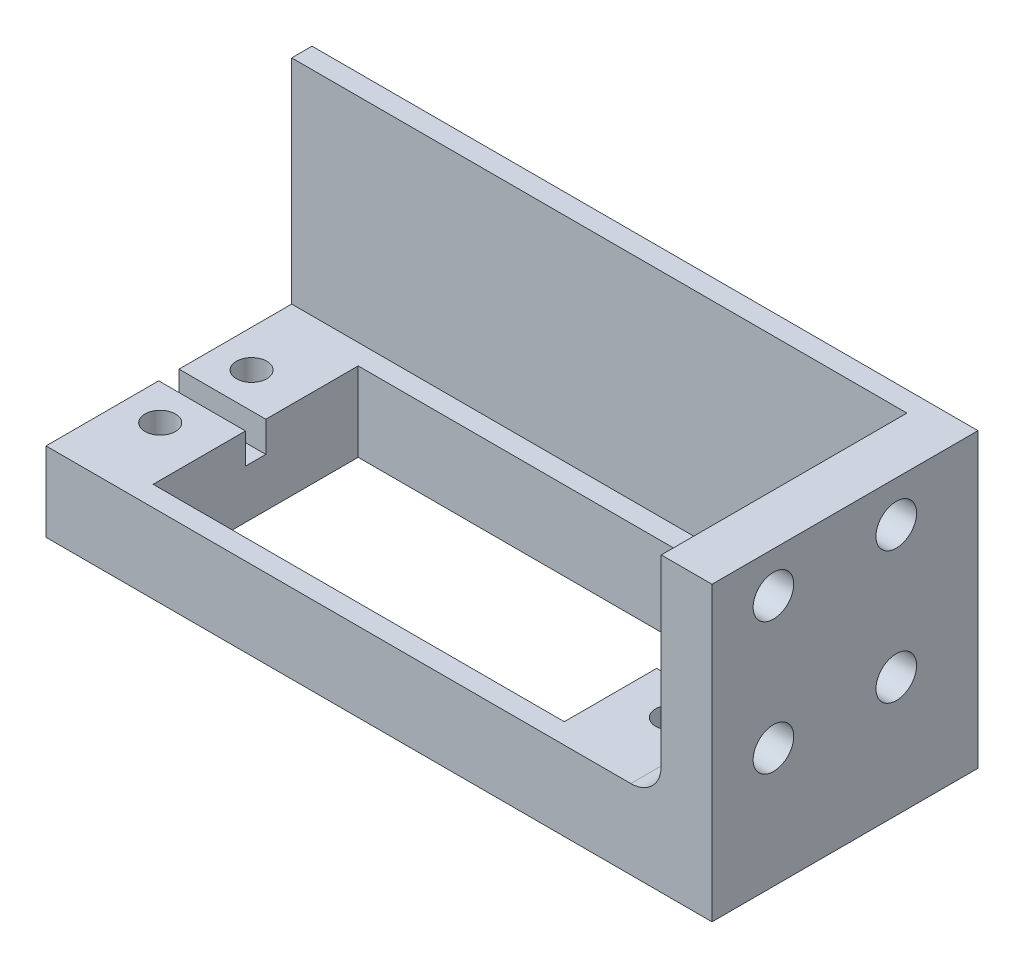
SolidWorks part; units mm, degrees
ref_plane "Front Plane" through (0, 0, 0) normal (0, 0, 1) x (1, 0, 0)
ref_plane "Top Plane" through (0, 0, 0) normal (0, 1, 0) x (1, 0, 0)
ref_plane "Right Plane" through (0, 0, 0) normal (1, 0, 0) x (0, 0, -1)
sketch "Sketch1" plane through (0, 0, 0) normal (0, 1, 0) x (1, 0, 0)
  line L0 (-101.8128, 12.4518) -> (-101.8128, 18.4813)
  line L1 (-101.8128, 21.4518) -> (-101.8128, 24.8665)
  line L2 (-94.5628, 5.4665) -> (-101.2128, 5.4665)
  line L3 (-95.1628, 6.0665) -> (-95.1628, 14.7945)
  line L4 (-54.8628, 14.7945) -> (-54.8628, 6.0665)
  line L5 (-48.2128, 18.4813) -> (-48.2128, 12.4518)
  line L6 (-85.1628, 25.4665) -> (-61.0205, 25.4665)
  line L7 (-95.2628, 25.4665) -> (-95.2628, 5.4665)
  line L8 (-101.8128, 25.4665) -> (-48.2128, 25.4665)
  line L9 (-101.8128, 25.4665) -> (-101.8128, 5.4665)
  line L10 (-101.8128, 5.4665) -> (-48.2128, 5.4665)
  line L11 (-48.2128, 25.4665) -> (-48.2128, 5.4665)
  line L12 (-95.1628, 25.4665) -> (-54.8628, 25.4665)
  line L13 (-95.1628, 25.4665) -> (-95.1628, 5.4665)
  line L14 (-95.1628, 5.4665) -> (-54.8628, 5.4665)
  line L15 (-54.8628, 25.4665) -> (-54.8628, 5.4665)
  line L17 (-54.7628, 25.4665) -> (-54.7628, 5.4665)
  line L19 (-95.2628, 25.5665) -> (-54.7628, 25.5665) construction
  line L20 (-95.2628, 5.3665) -> (-54.7628, 5.3665) construction
  line L22 (-95.2628, 25.5665) -> (-95.2628, 5.3665) construction
  line L23 (-54.7628, 25.5665) -> (-54.7628, 5.3665) construction
  circle A4 centre (-100.1628, 19.9665) radius 1.5
  circle A5 centre (-100.1628, 10.9665) radius 1.5
  circle A6 centre (-49.8628, 19.9665) radius 1.5
  circle A7 centre (-49.8628, 10.9665) radius 1.5
  dimension "D1" = 0.1
extrude "Boss-Extrude1" add sketch "Sketch1" along normal blind 7.8 contours L8 L17 L10 L11 L5 A7 A6 | L9 L10 L2 L7 L8 L1 L0 A5 A4
sketch "Sketch2" plane through (0, 7.8, 0) normal (0, 1, 0) x (1, 0, 0)
  line L5 (-101.8128, 25.4665) -> (-103.8128, 25.4665)
  line L6 (-101.8128, 25.4665) -> (-101.8128, 5.4665)
  line L7 (-101.8128, 5.4665) -> (-103.8128, 5.4665)
  line L8 (-101.8128, 25.4665) -> (-101.8128, 5.4665)
  line L9 (-101.8128, 5.4665) -> (-95.2628, 5.4665)
  line L10 (-95.2628, 5.4665) -> (-95.2628, 25.4665)
  line L11 (-95.2628, 25.4665) -> (-101.8128, 25.4665)
  line L12 (-101.8128, 25.4665) -> (-101.8128, 5.4665)
  line L13 (-101.8128, 5.4665) -> (-95.2628, 5.4665)
  line L14 (-95.2628, 5.4665) -> (-95.2628, 25.4665)
  line L15 (-95.2628, 25.4665) -> (-101.8128, 25.4665)
  line L16 (-103.8128, 25.4665) -> (-103.8128, 5.4665)
  line L17 (-48.2128, 25.4665) -> (-46.2128, 25.4665)
  line L18 (-48.2128, 25.4665) -> (-48.2128, 5.4665)
  line L19 (-48.2128, 5.4665) -> (-46.2128, 5.4665)
  line L20 (-46.2128, 25.4665) -> (-46.2128, 5.4665)
  line M11 (-48.2128, 5.4665) -> (-48.2128, 25.4665)
  dimension "D1" = 0
extrude "Boss-Extrude2" add sketch "Sketch2" against normal blind 7.8 contours L20 L17 L19 M11 | L5 L16 L7 L6
sketch "Sketch3" plane through (0, 7.8, 0) normal (0, 1, 0) x (1, 0, 0)
  line L0 (-54.7628, 25.4665) -> (-46.2128, 25.4665) construction
  line L1 (-95.2628, 25.4665) -> (-54.7628, 25.4665)
  line L2 (-95.2628, 25.4665) -> (-95.2628, 25.5665)
  line L3 (-95.2628, 25.5665) -> (-54.7628, 25.5665)
  line L4 (-54.7628, 25.4665) -> (-54.7628, 25.5665)
  line L5 (-95.2628, 5.4665) -> (-54.7628, 5.4665)
  line L6 (-95.2628, 5.4665) -> (-95.2628, 5.3665)
  line L7 (-95.2628, 5.3665) -> (-54.7628, 5.3665)
  line L8 (-54.7628, 5.4665) -> (-54.7628, 5.3665)
  line L9 (-103.8128, 25.4665) -> (-95.2628, 25.4665)
  line L10 (-103.8128, 25.4665) -> (-103.8128, 25.5665)
  line L11 (-103.8128, 25.5665) -> (-95.2628, 25.5665)
  line L12 (-95.2628, 25.4665) -> (-95.2628, 25.5665)
  line L13 (-54.7628, 25.5665) -> (-46.2128, 25.5665)
  line L14 (-54.7628, 25.5665) -> (-54.7628, 25.4665)
  line L15 (-54.7628, 25.4665) -> (-46.2128, 25.4665)
  line L16 (-46.2128, 25.5665) -> (-46.2128, 25.4665)
  line L17 (-103.8128, 5.4665) -> (-95.2628, 5.4665) construction
  line L18 (-103.8128, 5.4665) -> (-46.2128, 5.4665)
  line L19 (-103.8128, 5.4665) -> (-103.8128, 5.3665)
  line L20 (-103.8128, 5.3665) -> (-46.2128, 5.3665)
  line L21 (-46.2128, 5.4665) -> (-46.2128, 5.3665)
  line L22 (-103.8128, 25.4665) -> (-103.8128, 5.4665) construction
  line M5 (-95.2628, 25.4665) -> (-103.8128, 25.4665)
  line M7 (-103.8128, 5.4665) -> (-95.2628, 5.4665)
extrude "Boss-Extrude3" add sketch "Sketch3" against normal blind 7.8 contours L19 L20 L6 M7 | L11 L10 L2 M5 | L16 L13 L4 L15 | L21 L18 L8 L20
sketch "Sketch4" plane through (0, 7.8, 0) normal (0, 1, 0) x (1, 0, 0)
  line L1 (-103.8128, 25.5665) -> (-46.2128, 25.5665)
  line L2 (-103.8128, 25.5665) -> (-103.8128, 27.5665)
  line L3 (-103.8128, 27.5665) -> (-46.2128, 27.5665)
  line L4 (-46.2128, 25.5665) -> (-46.2128, 27.5665)
  line L5 (-103.8128, 5.3665) -> (-46.2128, 5.3665)
  line L6 (-103.8128, 5.3665) -> (-103.8128, 3.3665)
  line L7 (-103.8128, 3.3665) -> (-46.2128, 3.3665)
  line L8 (-46.2128, 5.3665) -> (-46.2128, 3.3665)
extrude "Boss-Extrude4" add sketch "Sketch4" against normal blind 7.8
sketch "Sketch5" plane through (0, 7.8, 0) normal (0, 1, 0) x (1, 0, 0)
  line L0 (-95.2628, 14.4665) -> (-103.8128, 16.4665) construction
  line L1 (-95.2628, 16.4665) -> (-103.8128, 14.4665) construction
  line L3 (-46.2128, 27.5665) -> (-46.2128, 3.3665) construction
  line L4 (-75.0128, 15.4665) -> (-75.0128, 20.7139)
  line L5 (-54.7628, 16.4665) -> (-46.2128, 16.4665)
  line L6 (-54.7628, 16.4665) -> (-54.7628, 14.4665)
  line L7 (-54.7628, 14.4665) -> (-46.2128, 14.4665)
  line L8 (-46.2128, 16.4665) -> (-46.2128, 14.4665)
  line L9 (-54.7628, 16.4665) -> (-46.2128, 14.4665) construction
  line L10 (-54.7628, 14.4665) -> (-46.2128, 16.4665) construction
  line L11 (-103.8128, 16.4665) -> (-103.8128, 14.4665)
  line L12 (-95.2628, 14.4665) -> (-103.8128, 14.4665)
  line L13 (-95.2628, 16.4665) -> (-95.2628, 14.4665)
  line L14 (-95.2628, 16.4665) -> (-103.8128, 16.4665)
  point P6 (-99.5378, 15.4665)
  point P10 (-50.4878, 15.4665)
  line M4 (-46.2128, 3.3665) -> (-46.2128, 27.5665)
  line M6 (-103.8128, 27.5665) -> (-103.8128, 3.3665)
  line M9 (-54.7628, 25.5665) -> (-54.7628, 5.3665)
  line M11 (-95.2628, 5.3665) -> (-95.2628, 25.5665)
extrude "Cut-Extrude1" cut sketch "Sketch5" against normal blind 3 contours L14 L12 M11 M6 | L7 L5 M9 M4
sketch "Sketch6" plane through (0, 7.8, 0) normal (0, 1, 0) x (1, 0, 0)
  line L0 (-82.1628, 15.4665) -> (-88.1628, 15.4665)
  line L1 (-95.2628, 15.4665) -> (-85.1628, 15.4665)
  line L2 (-95.2628, 14.4665) -> (-95.2628, 16.4665) construction
  line L3 (-97.661, -0.0334) -> (-97.661, 30.9666)
  line L4 (-72.661, -0.0334) -> (-72.661, 30.9666)
  line L5 (-93.161, -4.5334) -> (-77.161, -4.5334)
  line L6 (-93.161, 35.4666) -> (-77.161, 35.4666)
  line L7 (-103.8128, 16.4665) -> (-95.2628, 16.4665) construction
  line L8 (-95.2628, 16.4665) -> (-95.2628, 25.5665) construction
  line L9 (-95.2628, 25.5665) -> (-54.7628, 25.5665) construction
  line L10 (-54.7628, 25.5665) -> (-54.7628, 16.4665) construction
  line L11 (-54.7628, 16.4665) -> (-46.2128, 16.4665) construction
  line L12 (-46.2128, 16.4665) -> (-46.2128, 27.5665) construction
  line L13 (-46.2128, 27.5665) -> (-103.8128, 27.5665) construction
  line L14 (-103.8128, 27.5665) -> (-103.8128, 16.4665) construction
  line L15 (-95.2628, 5.3665) -> (-95.2628, 14.4665) construction
  line L16 (-95.2628, 14.4665) -> (-103.8128, 14.4665) construction
  line L17 (-103.8128, 14.4665) -> (-103.8128, 3.3665) construction
  line L18 (-103.8128, 3.3665) -> (-46.2128, 3.3665) construction
  line L19 (-46.2128, 3.3665) -> (-46.2128, 14.4665) construction
  line L20 (-46.2128, 14.4665) -> (-54.7628, 14.4665) construction
  line L21 (-54.7628, 14.4665) -> (-54.7628, 5.3665) construction
  line L22 (-54.7628, 5.3665) -> (-95.2628, 5.3665) construction
  line L23 (-103.8128, 16.4665) -> (-95.2628, 16.4665)
  line L24 (-95.2628, 16.4665) -> (-95.2628, 25.5665)
  line L25 (-95.2628, 25.5665) -> (-54.7628, 25.5665)
  line L26 (-54.7628, 25.5665) -> (-54.7628, 16.4665)
  line L27 (-54.7628, 16.4665) -> (-46.2128, 16.4665)
  line L28 (-46.2128, 16.4665) -> (-46.2128, 27.5665)
  line L29 (-46.2128, 27.5665) -> (-103.8128, 27.5665)
  line L30 (-103.8128, 27.5665) -> (-103.8128, 16.4665)
  line L31 (-95.2628, 5.3665) -> (-95.2628, 14.4665)
  line L32 (-95.2628, 14.4665) -> (-103.8128, 14.4665)
  line L33 (-103.8128, 14.4665) -> (-103.8128, 3.3665)
  line L34 (-103.8128, 3.3665) -> (-46.2128, 3.3665)
  line L35 (-46.2128, 3.3665) -> (-46.2128, 14.4665)
  line L36 (-46.2128, 14.4665) -> (-54.7628, 14.4665)
  line L37 (-54.7628, 14.4665) -> (-54.7628, 5.3665)
  line L38 (-54.7628, 5.3665) -> (-95.2628, 5.3665)
  circle A0 centre (-77.161, 30.9666) radius 1.5
  circle A1 centre (-93.161, 30.9666) radius 1.5
  circle A2 centre (-77.161, -0.0334) radius 1.5
  circle A3 centre (-93.161, -0.0334) radius 1.5
  circle A4 centre (-85.1628, 15.4665) radius 3
  circle A5 centre (-77.161, -0.0334) radius 4.5
  circle A6 centre (-93.161, -0.0334) radius 4.5
  circle A7 centre (-93.161, 30.9666) radius 4.5
  circle A8 centre (-77.161, 30.9666) radius 4.5
  line M9 (-46.2128, 27.5665) -> (-103.8128, 27.5665)
  dimension "D1" = 3
extrude "Boss-Extrude5" add sketch "Sketch6" against normal up to surface (7.8 mm away) contours A6 L34 L3 | A6 L34 A3 | A6 L5 A5 L34 | A5 L34 A2 | A5 L4 L34 | L29 A8 A0 | A8 L4 M9 | A8 L6 A7 M9 | L29 A7 A1 | A7 L3 M9 up to face at (-75.0128, 0, -15.4665)
sketch "Sketch7" plane through (0, 7.8, 0) normal (0, 1, 0) x (1, 0, 0)
  line L1 (-97.661, 27.5665) -> (-72.661, 27.5665)
  line L2 (-97.661, 27.5665) -> (-97.661, 3.3665)
  line L3 (-97.661, 3.3665) -> (-72.661, 3.3665)
  line L4 (-72.661, 27.5665) -> (-72.661, 3.3665)
  line L28 (-103.8128, 16.4665) -> (-95.2628, 16.4665)
  line L29 (-95.2628, 16.4665) -> (-95.2628, 25.5665)
  line L30 (-95.2628, 25.5665) -> (-54.7628, 25.5665)
  line L31 (-54.7628, 25.5665) -> (-54.7628, 16.4665)
  line L32 (-54.7628, 16.4665) -> (-46.2128, 16.4665)
  line L33 (-46.2128, 16.4665) -> (-46.2128, 27.5665)
  line L34 (-46.2128, 27.5665) -> (-72.661, 27.5665)
  line L35 (-72.661, 27.5665) -> (-72.661, 30.9666)
  line L36 (-77.161, 35.4666) -> (-93.161, 35.4666)
  line L37 (-97.661, 30.9666) -> (-97.661, 27.5665)
  line L38 (-97.661, 27.5665) -> (-103.8128, 27.5665)
  line L39 (-103.8128, 27.5665) -> (-103.8128, 16.4665)
  line L40 (-103.8128, 16.4665) -> (-95.2628, 16.4665)
  line L41 (-95.2628, 16.4665) -> (-95.2628, 25.5665)
  line L42 (-95.2628, 25.5665) -> (-54.7628, 25.5665)
  line L43 (-54.7628, 25.5665) -> (-54.7628, 16.4665)
  line L44 (-54.7628, 16.4665) -> (-46.2128, 16.4665)
  line L45 (-46.2128, 16.4665) -> (-46.2128, 27.5665)
  line L46 (-46.2128, 27.5665) -> (-72.661, 27.5665)
  line L47 (-72.661, 27.5665) -> (-72.661, 30.9666)
  line L48 (-77.161, 35.4666) -> (-93.161, 35.4666)
  line L49 (-97.661, 30.9666) -> (-97.661, 27.5665)
  line L50 (-97.661, 27.5665) -> (-103.8128, 27.5665)
  line L51 (-103.8128, 27.5665) -> (-103.8128, 16.4665)
  line L52 (-95.2628, 5.3665) -> (-95.2628, 14.4665)
  line L53 (-95.2628, 14.4665) -> (-103.8128, 14.4665)
  line L54 (-103.8128, 14.4665) -> (-103.8128, 3.3665)
  line L55 (-103.8128, 3.3665) -> (-97.661, 3.3665)
  line L56 (-97.661, 3.3665) -> (-97.661, -0.0334)
  line L57 (-93.161, -4.5334) -> (-77.161, -4.5334)
  line L58 (-72.661, -0.0334) -> (-72.661, 3.3665)
  line L59 (-72.661, 3.3665) -> (-46.2128, 3.3665)
  line L60 (-46.2128, 3.3665) -> (-46.2128, 14.4665)
  line L61 (-46.2128, 14.4665) -> (-54.7628, 14.4665)
  line L62 (-54.7628, 14.4665) -> (-54.7628, 5.3665)
  line L63 (-54.7628, 5.3665) -> (-95.2628, 5.3665)
  line L64 (-95.2628, 5.3665) -> (-95.2628, 14.4665)
  line L65 (-95.2628, 14.4665) -> (-103.8128, 14.4665)
  line L66 (-103.8128, 14.4665) -> (-103.8128, 3.3665)
  line L67 (-103.8128, 3.3665) -> (-97.661, 3.3665)
  line L68 (-97.661, 3.3665) -> (-97.661, -0.0334)
  line L69 (-93.161, -4.5334) -> (-77.161, -4.5334)
  line L70 (-72.661, -0.0334) -> (-72.661, 3.3665)
  line L71 (-72.661, 3.3665) -> (-46.2128, 3.3665)
  line L72 (-46.2128, 3.3665) -> (-46.2128, 14.4665)
  line L73 (-46.2128, 14.4665) -> (-54.7628, 14.4665)
  line L74 (-54.7628, 14.4665) -> (-54.7628, 5.3665)
  line L75 (-54.7628, 5.3665) -> (-95.2628, 5.3665)
  arc A4 (-72.661, 30.9666) -> (-77.161, 35.4666) centre (-77.161, 30.9666) ccw
  arc A5 (-93.161, 35.4666) -> (-97.661, 30.9666) centre (-93.161, 30.9666) ccw
  arc A6 (-72.661, 30.9666) -> (-77.161, 35.4666) centre (-77.161, 30.9666) ccw
  arc A7 (-93.161, 35.4666) -> (-97.661, 30.9666) centre (-93.161, 30.9666) ccw
  arc A8 (-97.661, -0.0334) -> (-93.161, -4.5334) centre (-93.161, -0.0334) ccw
  arc A9 (-77.161, -4.5334) -> (-72.661, -0.0334) centre (-77.161, -0.0334) ccw
  arc A10 (-97.661, -0.0334) -> (-93.161, -4.5334) centre (-93.161, -0.0334) ccw
  arc A11 (-77.161, -4.5334) -> (-72.661, -0.0334) centre (-77.161, -0.0334) ccw
  line M35 (-97.661, 3.3665) -> (-97.661, -0.0334)
  arc M36 (-97.661, -0.0334) -> (-93.161, -4.5334) centre (-93.161, -0.0334) ccw
  line M37 (-93.161, -4.5334) -> (-77.161, -4.5334)
  arc M38 (-77.161, -4.5334) -> (-72.661, -0.0334) centre (-77.161, -0.0334) ccw
  line M39 (-72.661, -0.0334) -> (-72.661, 3.3665)
  circle M45 centre (-93.161, -0.0334) radius 1.5
  circle M46 centre (-77.161, -0.0334) radius 1.5
  dimension "D1" = 0
  dimension "D2" = 0
extrude "Cut-Extrude2" cut sketch "Sketch7" against normal blind 4 contours L3 M35 M36 M37 M38 M39 M46 M45 | L48 A7 L49 L1 L47 A6
sketch "Sketch8" plane through (-46.2128, 0, 0) normal (1, 0, 0) x (0, 0, -1)
  line L1 (3.3665, 7.8) -> (27.5665, 7.8)
  line L2 (3.3665, 7.8) -> (3.3665, 0)
  line L3 (3.3665, 0) -> (27.5665, 0)
  line L4 (27.5665, 7.8) -> (27.5665, 0)
extrude "Boss-Extrude6" add sketch "Sketch8" along normal blind 5
sketch "Sketch10" plane through (0, 0, 0) normal (0, -1, 0) x (1, 0, 0)
  line L1 (-103.8128, -3.3665) -> (-41.2128, -3.3665)
  line L2 (-103.8128, -3.3665) -> (-103.8128, -27.5665)
  line L3 (-103.8128, -27.5665) -> (-41.2128, -27.5665)
  line L4 (-41.2128, -3.3665) -> (-41.2128, -27.5665)
  line L12 (-41.2128, -27.5665) -> (-41.2128, -3.3665)
  line L13 (-41.2128, -3.3665) -> (-72.661, -3.3665)
  line L14 (-72.661, -3.3665) -> (-72.661, 0.0334)
  line L15 (-77.161, 4.5334) -> (-93.161, 4.5334)
  line L16 (-97.661, 0.0334) -> (-97.661, -3.3665)
  line L17 (-97.661, -3.3665) -> (-103.8128, -3.3665)
  line L18 (-103.8128, -3.3665) -> (-103.8128, -27.5665)
  line L19 (-103.8128, -27.5665) -> (-97.661, -27.5665)
  line L20 (-97.661, -27.5665) -> (-97.661, -30.9666)
  line L21 (-93.161, -35.4666) -> (-77.161, -35.4666)
  line L22 (-72.661, -30.9666) -> (-72.661, -27.5665)
  line L23 (-72.661, -27.5665) -> (-41.2128, -27.5665)
  line L25 (-41.2128, -3.3665) -> (-72.661, -3.3665)
  line L26 (-72.661, -3.3665) -> (-72.661, 0.0334)
  line L27 (-77.161, 4.5334) -> (-93.161, 4.5334)
  line L28 (-97.661, 0.0334) -> (-97.661, -3.3665)
  line L29 (-97.661, -3.3665) -> (-103.8128, -3.3665)
  line L30 (-103.8128, -3.3665) -> (-103.8128, -27.5665)
  line L31 (-103.8128, -27.5665) -> (-97.661, -27.5665)
  line L32 (-97.661, -27.5665) -> (-97.661, -30.9666)
  line L33 (-93.161, -35.4666) -> (-77.161, -35.4666)
  line L34 (-72.661, -30.9666) -> (-72.661, -27.5665)
  line L35 (-72.661, -27.5665) -> (-41.2128, -27.5665)
  line L40 (-41.2128, -27.5665) -> (-41.2128, -3.3665)
  arc A4 (-72.661, 0.0334) -> (-77.161, 4.5334) centre (-77.161, 0.0334) ccw
  arc A5 (-93.161, 4.5334) -> (-97.661, 0.0334) centre (-93.161, 0.0334) ccw
  arc A6 (-97.661, -30.9666) -> (-93.161, -35.4666) centre (-93.161, -30.9666) ccw
  arc A7 (-77.161, -35.4666) -> (-72.661, -30.9666) centre (-77.161, -30.9666) ccw
  arc A8 (-72.661, 0.0334) -> (-77.161, 4.5334) centre (-77.161, 0.0334) ccw
  arc A9 (-93.161, 4.5334) -> (-97.661, 0.0334) centre (-93.161, 0.0334) ccw
  arc A10 (-97.661, -30.9666) -> (-93.161, -35.4666) centre (-93.161, -30.9666) ccw
  arc A11 (-77.161, -35.4666) -> (-72.661, -30.9666) centre (-77.161, -30.9666) ccw
  circle M17 centre (-93.161, -30.9666) radius 1.5
  circle M18 centre (-77.161, -30.9666) radius 1.5
  circle M19 centre (-93.161, 0.0334) radius 1.5
  circle M20 centre (-77.161, 0.0334) radius 1.5
  line M31 (-72.661, -3.3665) -> (-72.661, 0.0334)
  arc M32 (-72.661, 0.0334) -> (-77.161, 4.5334) centre (-77.161, 0.0334) ccw
  line M33 (-77.161, 4.5334) -> (-93.161, 4.5334)
  arc M34 (-93.161, 4.5334) -> (-97.661, 0.0334) centre (-93.161, 0.0334) ccw
  line M35 (-97.661, 0.0334) -> (-97.661, -3.3665)
  line M39 (-97.661, -27.5665) -> (-97.661, -30.9666)
  arc M40 (-97.661, -30.9666) -> (-93.161, -35.4666) centre (-93.161, -30.9666) ccw
  line M41 (-93.161, -35.4666) -> (-77.161, -35.4666)
  arc M42 (-77.161, -35.4666) -> (-72.661, -30.9666) centre (-77.161, -30.9666) ccw
  line M43 (-72.661, -30.9666) -> (-72.661, -27.5665)
  dimension "D1" = 0
extrude "Cut-Extrude3" cut sketch "Sketch10" against normal through all contours L1 M35 M31 M32 M33 M34 M19 M20 | L3 M39 M40 M41 M42 M43 M18 M17
sketch "Sketch15" plane through (-41.2128, 0, 0) normal (1, 0, 0) x (0, 0, -1)
  line L0 (27.5665, 0) -> (27.5665, 7.8) construction
  line L1 (3.3665, 7.8) -> (27.5665, 7.8)
  line L2 (3.3665, 7.8) -> (3.3665, 15.8)
  line L3 (3.3665, 15.8) -> (27.5665, 15.8)
  line L4 (27.5665, 7.8) -> (27.5665, 15.8)
  line L5 (15.4665, 15.8) -> (15.4665, 7.8)
  line L6 (3.3665, 7.8) -> (27.5665, 7.8)
  line L7 (3.3665, 7.8) -> (3.3665, 0)
  line L8 (3.3665, 0) -> (27.5665, 0)
  line L9 (27.5665, 7.8) -> (27.5665, 0)
  circle A0 centre (9.4165, 11.8) radius 2
  circle A1 centre (21.5165, 11.8) radius 2
  line M7 (27.5665, 7.8) -> (3.3665, 7.8)
extrude "Boss-Extrude10" add sketch "Sketch15" against normal blind 2 contours L5 L3 L2 L1 A0 | L3 L5 L4 A1 M7
sketch "Sketch16" plane through (-41.2128, 0, 0) normal (1, 0, 0) x (0, 0, -1)
  line L4 (3.3665, 15.8) -> (3.3665, 0)
  line L5 (3.3665, 0) -> (27.5665, 0)
  line L6 (27.5665, 0) -> (27.5665, 15.8)
  line L7 (27.5665, 15.8) -> (3.3665, 15.8)
  line L8 (3.3665, 15.8) -> (3.3665, 0)
  line L9 (3.3665, 0) -> (27.5665, 0)
  line L10 (27.5665, 0) -> (27.5665, 15.8)
  line L11 (27.5665, 15.8) -> (3.3665, 15.8)
  circle A1 centre (9.4165, 11.8) radius 2
  circle A2 centre (9.4165, 11.8) radius 2
  circle A3 centre (21.5165, 11.8) radius 2
  circle A4 centre (21.5165, 11.8) radius 2
  dimension "D1" = 0
  dimension "D2" = 0
  dimension "D3" = 0
extrude "Boss-Extrude11" add sketch "Sketch16" along normal blind 3
fillet "Fillet2" radius 3 1 edges at (-43.2128, 7.8, -15.4665)
sketch "Sketch17" plane through (-38.2128, 0, 0) normal (1, 0, 0) x (0, 0, -1)
  line L1 (3.3665, 15.8) -> (27.5665, 15.8)
  line L2 (3.3665, 15.8) -> (3.3665, 28.8)
  line L3 (3.3665, 28.8) -> (27.5665, 28.8)
  line L4 (27.5665, 15.8) -> (27.5665, 28.8)
  circle A6 centre (9.4165, 24.8) radius 2
  circle A7 centre (21.5165, 24.8) radius 2
extrude "Boss-Extrude13" add sketch "Sketch17" against normal blind 5
sketch "Sketch18" plane through (0, 0, -27.5665) normal (0, 0, -1) x (-1, 0, 0)
  line L1 (38.2128, 28.8) -> (103.8128, 28.8)
  line L2 (38.2128, 28.8) -> (38.2128, 0)
  line L3 (38.2128, 0) -> (103.8128, 0)
  line L4 (103.8128, 28.8) -> (103.8128, 0)
extrude "Boss-Extrude14" add sketch "Sketch18" along normal blind 2
